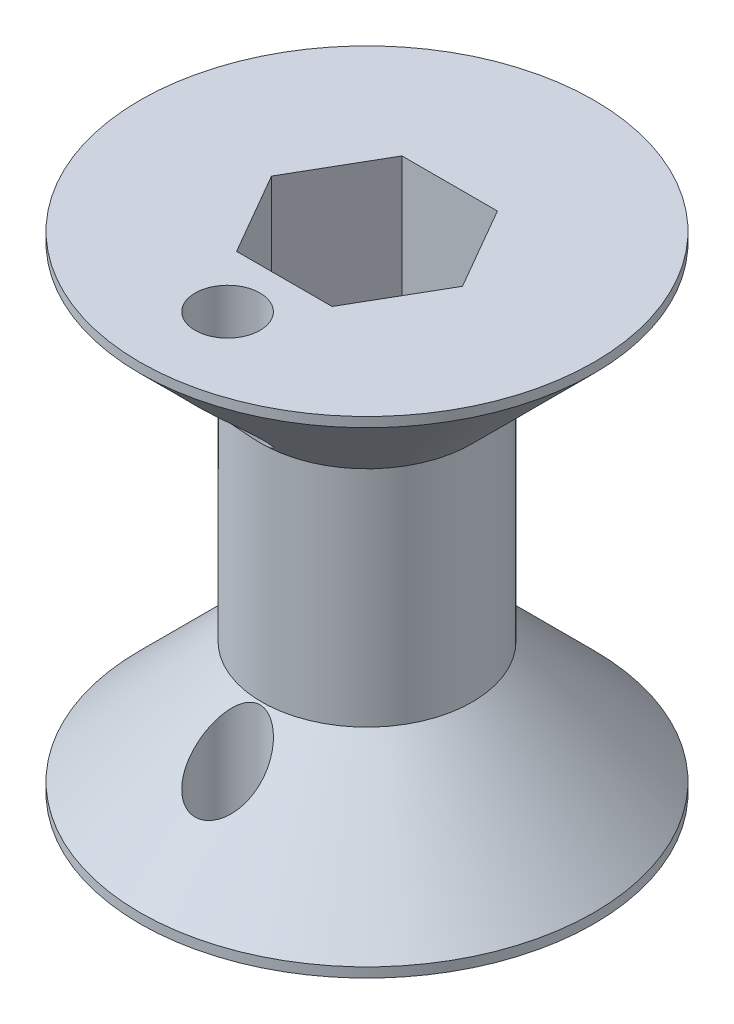
SolidWorks part; units mm, degrees
ref_plane "Front Plane" through (0, 0, 0) normal (0, 0, 1) x (1, 0, 0)
ref_plane "Top Plane" through (0, 0, 0) normal (0, 1, 0) x (1, 0, 0)
ref_plane "Right Plane" through (0, 0, 0) normal (1, 0, 0) x (0, 0, -1)
sketch "Sketch1" plane through (0, 0, 0) normal (1, 0, 0) x (0, 0, -1)
  line L0 (0, 0) -> (0, 19.05)
  line L1 (0, 19.05) -> (17.78, 19.05)
  line L2 (17.78, 19.05) -> (17.78, 18.288)
  line L3 (17.78, 18.288) -> (8.255, 8.763)
  line L4 (8.255, 8.763) -> (8.255, 0)
  line L5 (8.255, 0) -> (0, 0)
  dimension "D1" = 19.05
  dimension "D2" = 45
  dimension "D3" = 0.762
  dimension "D4" = 8.255
  dimension "D5" = 17.78
  dimension "D6" = 8.763
revolve "Revolve1" add sketch "Sketch1" angle 360 about L0
mirror "Mirror1" about plane through (0, 0, -8.255) normal (0, -1, 0) of "Revolve1"
sketch "Sketch2" plane through (0, 19.05, 0) normal (0, 1, 0) x (1, 0, 0)
  line L1 (-7.479, 0) -> (-3.7395, -6.477)
  line L2 (-3.7395, -6.477) -> (3.7395, -6.477)
  line L3 (3.7395, -6.477) -> (7.479, 0)
  line L4 (7.479, 0) -> (3.7395, 6.477)
  line L5 (3.7395, 6.477) -> (-3.7395, 6.477)
  line L6 (-3.7395, 6.477) -> (-7.479, 0)
  circle A0 centre (0, 0) radius 6.477 construction
  circle A1 centre (0, -10.922) radius 2.54
  circle A2 centre (0, 0) radius 17.78 construction
  dimension "D2" = 5.08
  dimension "D1" = 12.954
  dimension "." = 10.922
extrude "Cut-Extrude1" cut sketch "Sketch2" against normal through all
